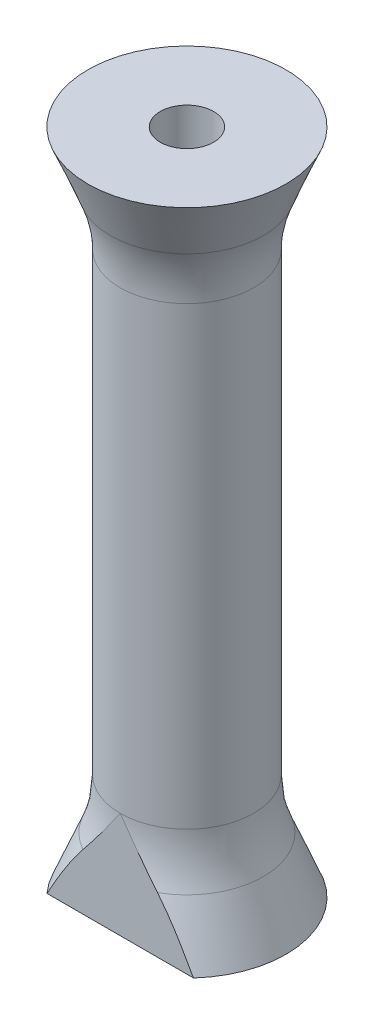
SolidWorks part; units mm, degrees
ref_plane "Front Plane" through (0, 0, 0) normal (0, 0, 1) x (1, 0, 0)
ref_plane "Top Plane" through (0, 0, 0) normal (0, 1, 0) x (1, 0, 0)
ref_plane "Right Plane" through (0, 0, 0) normal (1, 0, 0) x (0, 0, -1)
sketch "Sketch1" plane through (0, 0, 0) normal (0, 1, 0) x (1, 0, 0)
  circle A0 centre (0, 0) radius 6.35
  circle A1 centre (0, 0) radius 2.54
  dimension "D1" = 12.7
  dimension "D2" = 5.08
extrude "Boss-Extrude1" add sketch "Sketch1" along normal blind 63.5
sketch "Sketch2" plane through (0, 0, 0) normal (0, -1, 0) x (-1, 0, 0)
  circle A0 centre (0, 0) radius 9.525
  circle A1 centre (0, 0) radius 2.54
  dimension "D1" = 19.05
extrude "Boss-Extrude2" add sketch "Sketch2" against normal blind 7.62
chamfer "Chamfer1" distance 3.175 angle 68 1 edges at (0, 7.62, -9.525) first distance on face at (0, 7.62, -9.525)
fillet "Fillet1" radius 12.7 1 edges at (0, 7.62, -6.35)
sketch "Sketch3" plane through (0, 63.5, 0) normal (0, 1, 0) x (1, 0, 0)
  circle A0 centre (0, 0) radius 9.525
  circle A1 centre (0, 0) radius 2.54
  dimension "D1" = 19.05
extrude "Boss-Extrude3" add sketch "Sketch3" against normal blind 7.62
chamfer "Chamfer2" distance 3.175 angle 68 1 edges at (0, 55.88, 9.525) first distance on face at (0, 55.88, 9.525)
fillet "Fillet2" radius 12.7 1 edges at (0, 55.88, 6.35)
sketch "Sketch4" plane through (0, 0, 0) normal (0, 0, 1) x (1, 0, 0)
  line L1 (-14.5993, 37.9681) -> (14.5993, 37.9681)
  line L2 (-14.5993, 37.9681) -> (-14.5993, -4.7123)
  line L3 (-14.5993, -4.7123) -> (14.5993, -4.7123)
  line L4 (14.5993, 37.9681) -> (14.5993, -4.7123)
  line L5 (-14.5993, 37.9681) -> (14.5993, -4.7123) construction
  line L6 (-14.5993, -4.7123) -> (14.5993, 37.9681) construction
  point P0 (0, 16.6279)
extrude "Cut-Extrude1" cut sketch "Sketch4" along normal through all from offset 6.35
